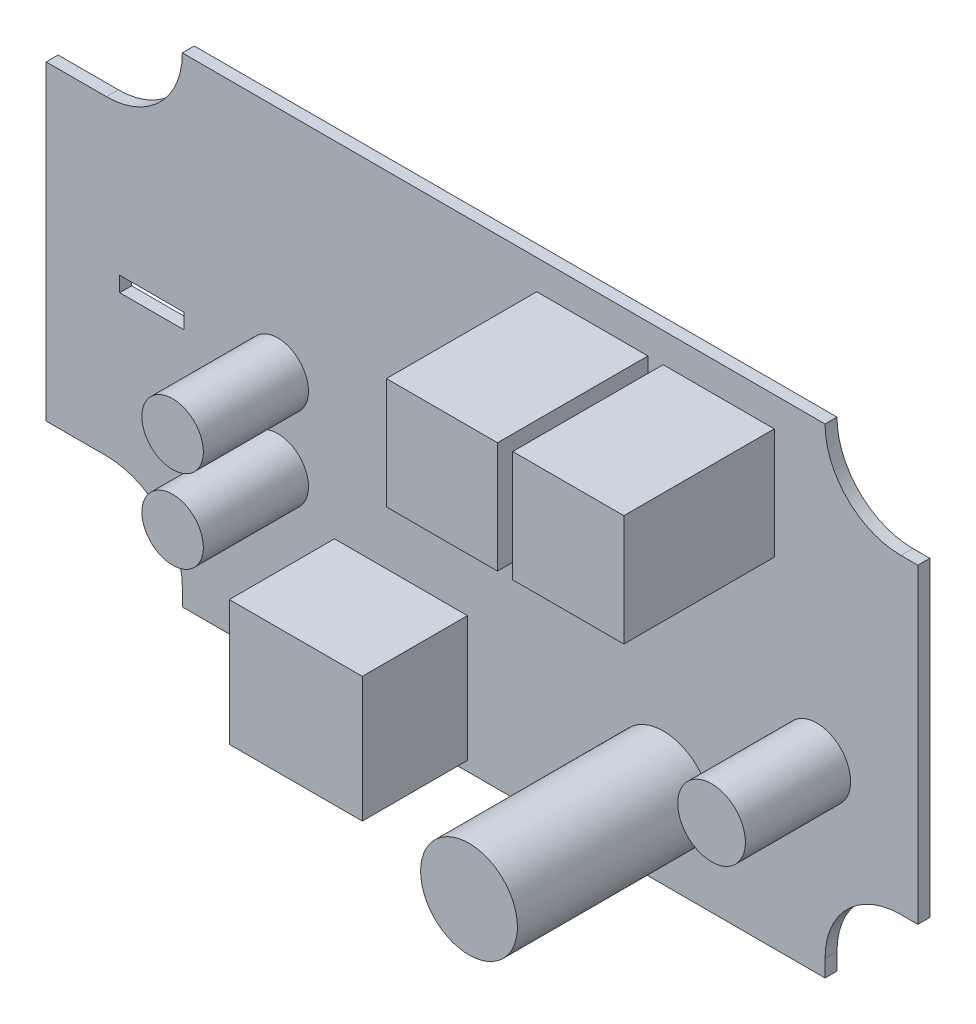
SolidWorks part; units mm, degrees
ref_plane "Front Plane" through (0, 0, 0) normal (0, 0, 1) x (1, 0, 0)
ref_plane "Top Plane" through (0, 0, 0) normal (0, 1, 0) x (1, 0, 0)
ref_plane "Right Plane" through (0, 0, 0) normal (1, 0, 0) x (0, 0, -1)
sketch "Sketch1" plane through (0, 0, 0) normal (0, 0, 1) x (1, 0, 0)
  line L0 (-42.3541, 30.2967) -> (-52.3541, 30.2967) construction
  line L1 (42.3541, -30.7033) -> (42.3541, -32.9433)
  line L2 (-52.3541, -20.7033) -> (-60.3013, -20.7033)
  line L3 (-42.3541, 30.2967) -> (42.3541, 30.2967)
  line L4 (52.3541, -20.7033) -> (54.5933, -20.7033)
  line L5 (-52.3541, 30.2967) -> (-52.3541, 20.2967) construction
  line L6 (-52.3541, -20.7033) -> (-52.3541, -30.7033) construction
  line L7 (-52.3541, -30.7033) -> (-42.3541, -30.7033) construction
  line L8 (42.3541, -30.7033) -> (52.3541, -30.7033) construction
  line L9 (52.3541, -30.7033) -> (52.3541, -20.7033) construction
  line L10 (52.3541, 20.2967) -> (52.3541, 30.2967) construction
  line L11 (52.3541, 30.2967) -> (42.3541, 30.2967) construction
  line L12 (54.5933, -20.7033) -> (54.5933, 20.2967)
  line L13 (-60.3013, -20.7033) -> (-60.3013, 20.2967)
  line L14 (-60.3013, 20.2967) -> (-52.3541, 20.2967)
  line L15 (54.5933, 20.2967) -> (52.3541, 20.2967)
  line L16 (42.3541, -32.9433) -> (-42.3541, -32.9433)
  line L17 (-42.3541, -32.9433) -> (-42.3541, -30.7033)
  line L18 (-50.6088, -0.2033) -> (-60.3013, -0.2033) construction
  line L19 (-42.1088, -1.2033) -> (-50.6088, -1.2033)
  line L20 (-42.1088, -1.2033) -> (-42.1088, 0.7967)
  line L21 (0, -32.9433) -> (0, 0) construction
  line L22 (-42.1088, 0.7967) -> (-50.6088, 0.7967)
  line L23 (-50.6088, -1.2033) -> (-50.6088, 0.7967)
  arc A0 (-42.3541, 30.2967) -> (-52.3541, 20.2967) centre (-52.3541, 30.2967) cw
  arc A2 (-52.3541, -20.7033) -> (-42.3541, -30.7033) centre (-52.3541, -30.7033) cw
  arc A4 (42.3541, 30.2967) -> (52.3541, 20.2967) centre (52.3541, 30.2967) ccw
  arc A5 (52.3541, -20.7033) -> (42.3541, -30.7033) centre (52.3541, -30.7033) ccw
  point P24 (-46.3588, 0.7967)
  dimension "D1" = 41
  dimension "D2" = 2
  dimension "D3" = 10
  dimension "D4" = 8.5
  dimension "D5" = 84.7082
  dimension "D6" = 2.24
  dimension "D7" = 7.9472
  dimension "D8" = 2.2392
  dimension "D9" = 13.9425
extrude "Boss-Extrude1" add sketch "Sketch1" along normal blind 1.5748
sketch "Sketch2" plane through (0, 0, 1.5748) normal (0, 0, 1) x (1, 0, 0)
  line L1 (4.3619, 26.3914) -> (19.0119, 26.3914)
  line L2 (4.3619, 26.3914) -> (4.3619, 11.7414)
  line L3 (4.3619, 11.7414) -> (19.0119, 11.7414)
  line L4 (19.0119, 26.3914) -> (19.0119, 11.7414)
  line L5 (21.0119, 26.3914) -> (35.6619, 26.3914)
  line L6 (21.0119, 26.3914) -> (21.0119, 11.7414)
  line L7 (21.0119, 11.7414) -> (35.6619, 11.7414)
  line L8 (35.6619, 26.3914) -> (35.6619, 11.7414)
  dimension "D1" = 2
  dimension "D2" = 14.65
extrude "Boss-Extrude2" add sketch "Sketch2" along normal blind 19.82
sketch "Sketch3" plane through (0, 0, 1.5748) normal (0, 0, 1) x (1, 0, 0)
  circle A0 centre (21.0509, -21.7791) radius 6.38
  dimension "D1" = 12.76
extrude "Boss-Extrude3" add sketch "Sketch3" along normal blind 25.62
sketch "Sketch4" plane through (0, 0, 1.5748) normal (0, 0, 1) x (1, 0, 0)
  line L1 (-22.3027, -15.1438) -> (-4.7739, -15.1438)
  line L2 (-22.3027, -15.1438) -> (-22.3027, -31.671)
  line L3 (-22.3027, -31.671) -> (-4.7739, -31.671)
  line L4 (-4.7739, -15.1438) -> (-4.7739, -31.671)
  circle A0 centre (-29.7754, 0) radius 4.05
  circle A1 centre (-29.7754, -10.91) radius 4.05
  circle A2 centre (41.2613, -8.8411) radius 4.4585
  dimension "D1" = 8.1
  dimension "D2" = 16.5272
  dimension "D4" = 8.9169
  dimension "D3" = 17.5288
extrude "Boss-Extrude4" add sketch "Sketch4" along normal blind 13.86
